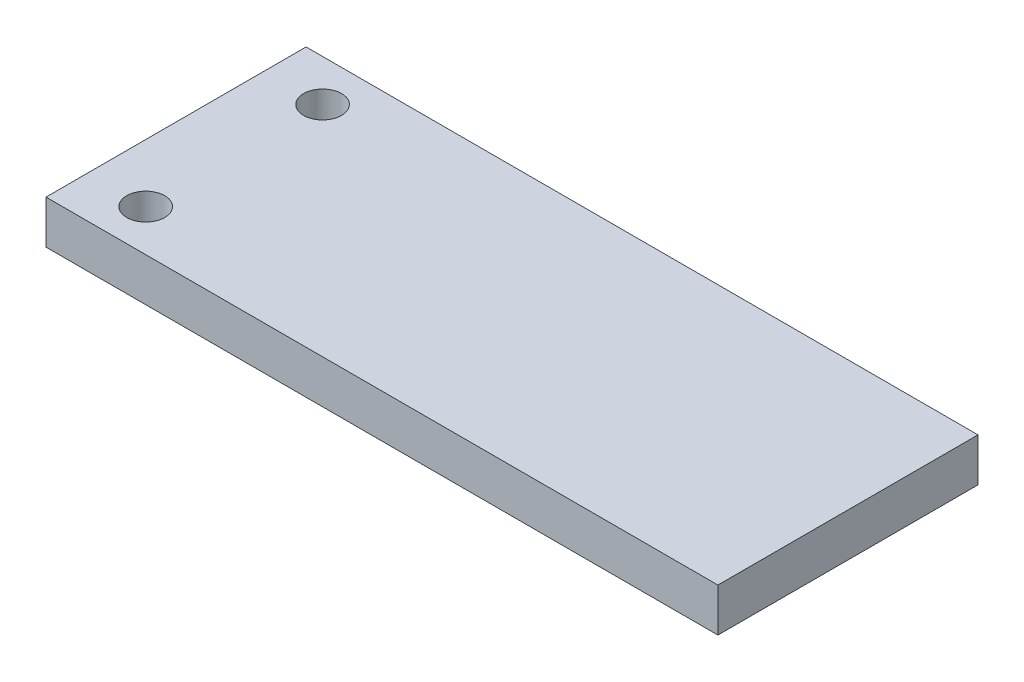
SolidWorks part; units mm, degrees
ref_plane "Front Plane" through (0, 0, 0) normal (0, 0, 1) x (1, 0, 0)
ref_plane "Top Plane" through (0, 0, 0) normal (0, 1, 0) x (1, 0, 0)
ref_plane "Right Plane" through (0, 0, 0) normal (1, 0, 0) x (0, 0, -1)
sketch "Sketch1" plane through (0, 0, 0) normal (0, 1, 0) x (1, 0, 0)
  line L0 (98.425, 38.1) -> (98.425, 0)
  line L1 (0, 0) -> (98.425, 0)
  line L2 (0, 0) -> (0, 38.1)
  line L3 (0, 38.1) -> (98.425, 38.1)
  line L4 (101.6, -0.753) -> (101.6, 38.1) construction
  dimension "D1" = 38.1
  dimension "D2" = 101.6
  dimension "D3" = 3.175
extrude "Boss-Extrude1" add sketch "Sketch1" along normal blind 6.35
sketch "Sketch2" plane through (0, 0, 0) normal (0, -1, 0) x (1, 0, 0)
  line L0 (98.425, -19.05) -> (49.6501, -19.05) construction
  line L1 (98.425, 0) -> (98.425, -38.1) construction
  circle A0 centre (8.509, -6.096) radius 2.7781
  circle A1 centre (8.509, -32.004) radius 2.7781
  dimension "D1" = 5.5562
extrude "Cut-Extrude1" cut sketch "Sketch2" against normal through all
